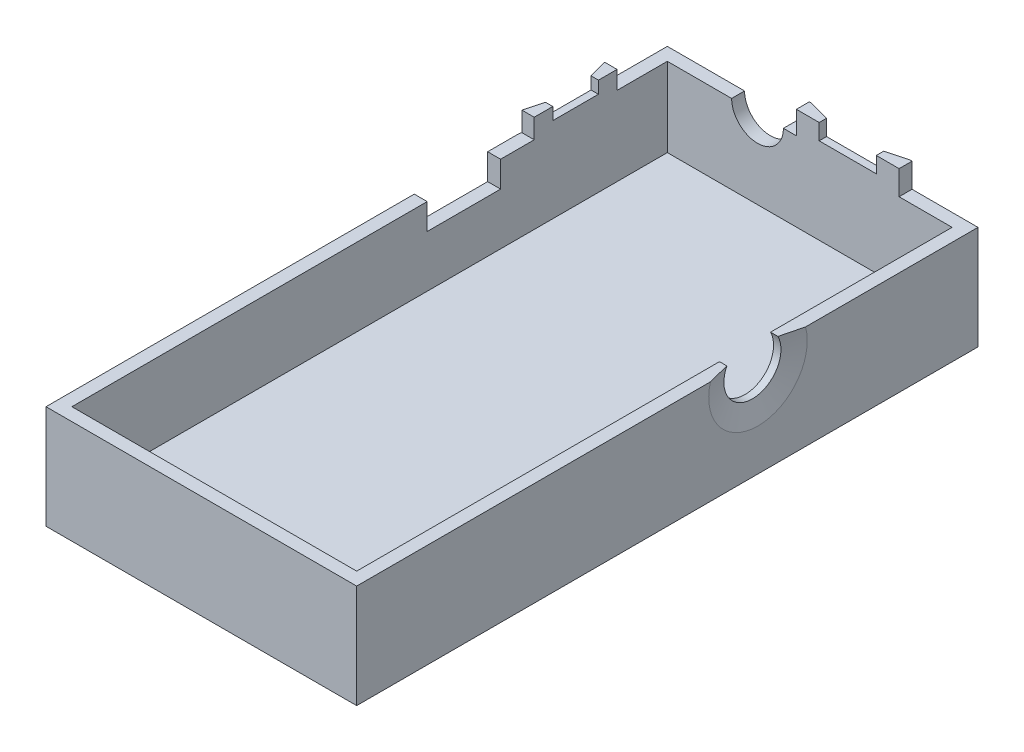
SolidWorks part; units mm, degrees
ref_plane "Front Plane" through (0, 0, 0) normal (0, 0, 1) x (1, 0, 0)
ref_plane "Top Plane" through (0, 0, 0) normal (0, 1, 0) x (1, 0, 0)
ref_plane "Right Plane" through (0, 0, 0) normal (1, 0, 0) x (0, 0, -1)
sketch "Sketch1" plane through (0, 0, 0) normal (0, 1, 0) x (1, 0, 0)
  line L1 (0, 0) -> (-38.1, 0)
  line L2 (0, 0) -> (0, -76.2)
  line L3 (0, -76.2) -> (-38.1, -76.2)
  line L4 (-38.1, 0) -> (-38.1, -76.2)
  dimension "D1" = 38.1
  dimension "D2" = 76.2
extrude "Boss-Extrude1" add sketch "Sketch1" along normal blind 15.875
sketch "Sketch4" plane through (0, 15.875, 0) normal (0, 1, 0) x (1, 0, 0)
  line L0 (0, 0) -> (-38.1, 0) construction
  line L1 (-36.5125, -1.5875) -> (-1.5875, -1.5875)
  line L2 (-36.5125, -1.5875) -> (-36.5125, -74.6125)
  line L3 (-36.5125, -74.6125) -> (-1.5875, -74.6125)
  line L4 (-1.5875, -1.5875) -> (-1.5875, -74.6125)
  line L5 (-38.1, 0) -> (-38.1, -76.2) construction
  line L6 (-38.1, -76.2) -> (0, -76.2) construction
  line L7 (0, -76.2) -> (0, 0) construction
  dimension "D1" = 1.5875
  dimension "D2" = 1.5875
  dimension "D3" = 1.5875
  dimension "D4" = 1.5875
extrude "Cut-Extrude2" cut sketch "Sketch4" against normal blind 12.7
sketch "Sketch5" plane through (0, 0, 0) normal (1, 0, 0) x (0, 0, -1)
  line L0 (0, 12.7) -> (-23.8514, 12.7)
  line L1 (-30.1152, 12.7) -> (-76.2, 12.7)
  line L2 (-76.2, 12.7) -> (-76.2, 15.875)
  line L3 (-76.2, 15.875) -> (0, 15.875)
  line L4 (0, 15.875) -> (0, 12.7)
  arc A0 (-30.1152, 12.7) -> (-23.8514, 12.7) centre (-26.9833, 11.1375) ccw
extrude "Cut-Extrude3" cut sketch "Sketch5" against normal blind 1.5875
chamfer "Chamfer1" distance 2.54 angle 15 1 edges at (0, 7.6375, 26.9833) first distance on face at (0, 7.6229, 34.3944)
sketch "Sketch6" plane through (0, 0, 0) normal (0, 0, -1) x (-1, 0, 0)
  line L0 (1.5875, 12.7) -> (8.0883, 12.7)
  line L1 (8.0883, 12.7) -> (8.0883, 15.6875)
  line L2 (8.0883, 15.6875) -> (10.8883, 15.6875)
  line L3 (10.8883, 15.6875) -> (10.8883, 13.7375)
  line L4 (8.0883, 13.7375) -> (20.6883, 13.7375) construction
  line L5 (10.8883, 13.7375) -> (17.8883, 13.7375)
  line L6 (17.8883, 13.7375) -> (17.8883, 15.6875)
  line L7 (17.8883, 15.6875) -> (20.6883, 15.6875)
  line L8 (20.6883, 15.6875) -> (20.6883, 12.8725)
  line L9 (20.6883, 12.8725) -> (22.2783, 12.8725)
  line L10 (28.6283, 12.8725) -> (38.1, 12.8725)
  line L11 (38.1, 12.8725) -> (38.1, 15.875)
  line L12 (38.1, 15.875) -> (1.5875, 15.875)
  line L13 (1.5875, 15.875) -> (1.5875, 12.7)
  line L14 (20.6883, 12.8725) -> (20.6883, 15.6875) construction
  line L15 (38.1, 12.8725) -> (28.6283, 12.8725) construction
  line L16 (22.2783, 12.8725) -> (20.6883, 12.8725) construction
  arc A0 (22.2783, 12.8725) -> (28.6283, 12.8725) centre (25.4533, 12.8725) ccw
  arc A1 (28.6283, 12.8725) -> (22.2783, 12.8725) centre (25.4533, 12.8725) ccw construction
extrude "Cut-Extrude4" cut sketch "Sketch6" against normal blind 1.5875
chamfer "Chamfer2" distance 2.54 angle 15 3 edges at (-10.8883, 14.7125, 0) (-17.8883, 14.7125, 0) (-14.3883, 13.7375, 0) first distance on face at (-17.3009, 11.71, 0)
sketch "Sketch7" plane through (0, 0, 76.2) normal (0, 0, 1) x (1, 0, 0)
  line L0 (-1.5875, 12.7) -> (-36.5125, 12.7)
  line L1 (-38.1, 12.7) -> (0, 12.7) construction
  line L2 (-36.5125, 12.7) -> (-36.5125, 15.875)
  line L3 (-36.5125, 15.875) -> (-1.5875, 15.875)
  line L4 (-1.5875, 15.875) -> (-1.5875, 12.7)
extrude "Cut-Extrude5" cut sketch "Sketch7" against normal blind 1.5875
sketch "Sketch8" plane through (-38.1, 0, 0) normal (-1, 0, 0) x (0, 0, 1)
  line L0 (76.2, 12.7) -> (31.0375, 12.7)
  line L1 (31.0375, 12.7) -> (31.0375, 9.525)
  line L2 (31.0375, 17.6375) -> (31.0375, 5.0375) construction
  line L3 (31.0375, 9.525) -> (22.0375, 9.525)
  line L4 (22.0375, 17.6375) -> (22.0375, 5.0375) construction
  line L5 (22.0375, 9.525) -> (22.0375, 12.7)
  line L6 (22.0375, 12.7) -> (17.9131, 12.7)
  line L7 (17.9131, 12.7) -> (17.9131, 15.0975)
  line L8 (17.9131, 15.0975) -> (15.6331, 15.0975)
  line L9 (15.6331, 15.0975) -> (15.6331, 13.5975)
  line L10 (15.7581, 13.5975) -> (15.5081, 13.5975) construction
  line L11 (15.6331, 13.5975) -> (10.0381, 13.5975)
  line L12 (10.0381, 13.5975) -> (10.0331, 15.0975)
  line L13 (10.0331, 13.7975) -> (10.0331, 16.3975) construction
  line L14 (10.0331, 15.0975) -> (7.7531, 15.0975)
  line L16 (7.7531, 15.0975) -> (7.7531, 12.8725)
  line L17 (7.7531, 12.8725) -> (1.5875, 12.8725)
  line L18 (1.5875, 12.8725) -> (1.5875, 15.875)
  line L19 (1.5875, 15.875) -> (76.2, 15.875)
  line L20 (76.2, 15.875) -> (76.2, 12.7)
  line L21 (7.7531, 15.0975) -> (7.7531, 12.8725) construction
  dimension "D1" = 3.175
extrude "Cut-Extrude6" cut sketch "Sketch8" against normal blind 1.5875
chamfer "Chamfer3" distance 2.54 angle 15 3 edges at (-38.1, 14.3475, 10.0356) (-38.1, 13.5975, 12.8356) (-38.1, 14.3475, 15.6331) first distance on face at (-38.1, 11.4488, 22.5762)
